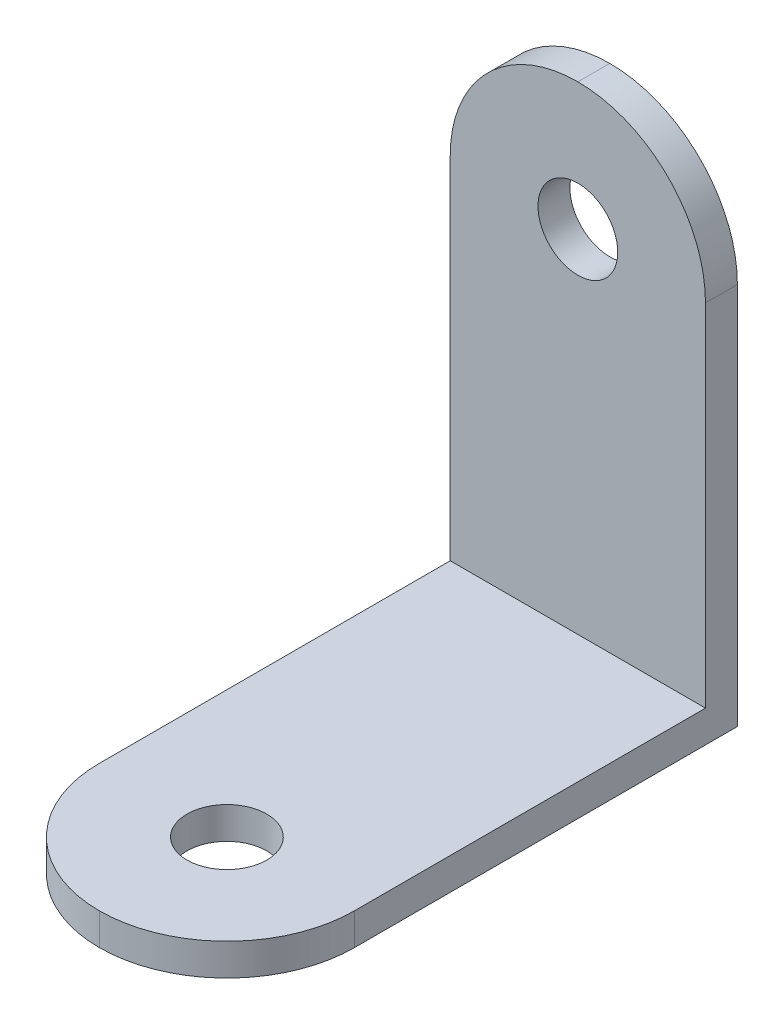
SolidWorks part; units mm, degrees
ref_plane "前视基准面" through (0, 0, 0) normal (0, 0, 1) x (1, 0, 0)
ref_plane "上视基准面" through (0, 0, 0) normal (0, 1, 0) x (1, 0, 0)
ref_plane "右视基准面" through (0, 0, 0) normal (1, 0, 0) x (0, 0, -1)
sketch "草图1" plane through (0, 0, 0) normal (0, 0, 1) x (1, 0, 0)
  line L1 (0, 0) -> (16, 0)
  line L2 (0, 0) -> (0, 2)
  line L3 (0, 2) -> (16, 2)
  line L4 (16, 0) -> (16, 2)
extrude "凸台-拉伸1" add sketch "草图1" along normal blind 30
fillet "圆角1" radius 8 1 edges at (0, 1, 30)
fillet "圆角2" radius 8 1 edges at (16, 1, 30)
sketch "草图2" plane through (0, 0, 0) normal (0, 1, 0) x (1, 0, 0)
  line L1 (0, 0) -> (16, 0)
  line L2 (0, 0) -> (0, 2)
  line L3 (0, 2) -> (16, 2)
  line L4 (16, 0) -> (16, 2)
extrude "凸台-拉伸2" add sketch "草图2" along normal blind 32
fillet "圆角3" radius 8 1 edges at (16, 32, -1)
fillet "圆角4" radius 8 1 edges at (0, 32, -1)
sketch "草图3" plane through (0, 0, 0) normal (0, 0, 1) x (1, 0, 0)
  circle A0 centre (8, 24) radius 2.5
  circle A1 centre (8, 40) radius 2.5
  dimension "D1" = 16
sketch "草图4" plane through (0, 2, 0) normal (0, 1, 0) x (1, 0, 0)
  circle A0 centre (8, -22) radius 2.5
extrude "切除-拉伸2" cut sketch "草图4" against normal blind 2
extrude "切除-拉伸3" cut sketch "草图3" against normal blind 2
